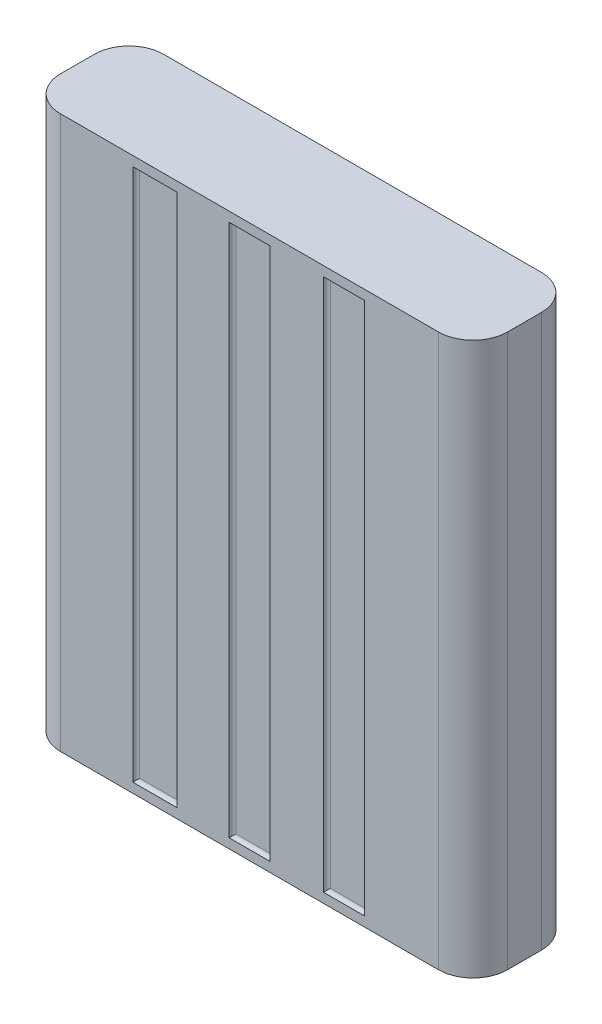
SolidWorks part; units mm, degrees
ref_plane "Front Plane" through (0, 0, 0) normal (0, 0, 1) x (1, 0, 0)
ref_plane "Top Plane" through (0, 0, 0) normal (0, 1, 0) x (1, 0, 0)
ref_plane "Right Plane" through (0, 0, 0) normal (1, 0, 0) x (0, 0, -1)
sketch "Sketch1" plane through (0, 0, 0) normal (0, 1, 0) x (1, 0, 0)
  line L1 (-6.4751, 1.4928) -> (6.4751, 1.4928)
  line L2 (-6.4751, 1.4928) -> (-6.4751, -1.4928)
  line L3 (-6.4751, -1.4928) -> (6.4751, -1.4928)
  line L4 (6.4751, 1.4928) -> (6.4751, -1.4928)
  line L5 (-6.4751, 1.4928) -> (6.4751, -1.4928) construction
  line L6 (-6.4751, -1.4928) -> (6.4751, 1.4928) construction
  point P0 (0, 0)
extrude "Boss-Extrude1" add sketch "Sketch1" along normal blind 16
fillet "Fillet1" radius 1 4 edges at (6.4751, 8, -1.4928) (6.4751, 8, 1.4928) (-6.4751, 8, -1.4928) (-6.4751, 8, 1.4928)
sketch "Sketch2" plane through (0, 0, -1.4928) normal (0, 0, -1) x (-1, 0, 0)
  line L0 (5.4751, 0) -> (5.4751, 16) construction
  line L1 (-5.4751, 10.8394) -> (5.4751, 10.8394)
  line L2 (-5.4751, 10.8394) -> (-5.4751, 10.567)
  line L3 (-5.4751, 10.567) -> (5.4751, 10.567)
  line L4 (5.4751, 10.8394) -> (5.4751, 10.567)
  line L5 (-5.4751, 16) -> (-5.4751, 0) construction
extrude "Boss-Extrude2" add sketch "Sketch2" along normal blind 0.1
fillet "Fillet2" radius 0.1 4 edges at (0, 10.8394, -1.5928) (-5.4751, 10.7032, -1.5928) (0, 10.567, -1.5928) (5.4751, 10.7032, -1.5928)
sketch "Sketch5" plane through (0, 0, -1.5928) normal (0, 0, -1) x (-1, 0, 0)
  line L0 (-5.4751, 10.8394) -> (-5.3751, 10.7394) construction
  line L3 (-5.3751, 10.567) -> (5.4751, 10.567)
  line L4 (5.4751, 10.7394) -> (5.4751, 10.567)
  line L5 (-5.3751, 10.567) -> (-5.4751, 10.567)
  line L7 (-5.3751, 10.8394) -> (-5.4751, 10.8394)
  line L8 (-5.4751, 10.567) -> (-5.4751, 10.8394)
  line L9 (-5.4751, 10.8394) -> (-5.4751, 10.567) construction
  line L11 (-5.3751, 10.8394) -> (5.4751, 10.8394)
  line L14 (5.4751, 10.8394) -> (5.4751, 10.7394)
extrude "Cut-Extrude2" cut sketch "Sketch5" against normal blind 0.1
sketch "Sketch6" plane through (0, 0, -1.4928) normal (0, 0, -1) x (-1, 0, 0)
  line L8 (-3.3309, 15.7209) -> (-2.1442, 15.7209)
  line L9 (-3.3309, 15.7209) -> (-3.3309, 0.2791)
  line L10 (-3.3309, 0.2791) -> (-2.1442, 0.2791)
  line L11 (-2.1442, 15.7209) -> (-2.1442, 0.2791)
  line L14 (-0.5877, 15.7209) -> (0.5877, 15.7209)
  line L15 (-0.5877, 15.7209) -> (-0.5877, 0.2791)
  line L16 (-0.5877, 0.2791) -> (0.5877, 0.2791)
  line L17 (0.5877, 15.7209) -> (0.5877, 0.2791)
  line L20 (2.0968, 15.7209) -> (3.3783, 15.7209)
  line L21 (2.0968, 15.7209) -> (2.0968, 0.2791)
  line L22 (2.0968, 0.2791) -> (3.3783, 0.2791)
  line L23 (3.3783, 15.7209) -> (3.3783, 0.2791)
  point P10 (-2.7375, 8)
  point P22 (2.7375, 8)
extrude "Cut-Extrude3" cut sketch "Sketch6" against normal blind 0.1 contours L23 L22 L21 L20 | L17 L16 L15 L14 | L11 L10 L9 L8
sketch "Sketch10" plane through (0, 0, 1.4928) normal (0, 0, 1) x (1, 0, 0)
  line L1 (3.3309, 15.7209) -> (2.1442, 15.7209)
  line L2 (3.3309, 15.7209) -> (3.3309, 0.2791)
  line L3 (3.3309, 0.2791) -> (2.1442, 0.2791)
  line L4 (2.1442, 15.7209) -> (2.1442, 0.2791)
  line L5 (0.5877, 15.7209) -> (-0.5877, 15.7209)
  line L6 (0.5877, 15.7209) -> (0.5877, 0.2791)
  line L7 (0.5877, 0.2791) -> (-0.5877, 0.2791)
  line L8 (-0.5877, 15.7209) -> (-0.5877, 0.2791)
  line L9 (-2.0968, 15.7209) -> (-3.3783, 15.7209)
  line L10 (-2.0968, 15.7209) -> (-2.0968, 0.2791)
  line L11 (-2.0968, 0.2791) -> (-3.3783, 0.2791)
  line L12 (-3.3783, 15.7209) -> (-3.3783, 0.2791)
extrude "Cut-Extrude4" cut sketch "Sketch10" against normal blind 0.1 contours L6 L5 L8 L7 | L2 L1 L4 L3 | L10 L9 L12 L11
fillet "Fillet6" radius 0.1 12 edges at (2.1442, 8, 1.3928) (2.7375, 15.7209, 1.3928) (3.3309, 8, 1.3928) (2.7375, 0.2791, 1.3928) (-0.5877, 8, 1.3928) (0, 15.7209, 1.3928) (0.5877, 8, 1.3928) (0, 0.2791, 1.3928) (-3.3783, 8, 1.3928) (-2.7375, 15.7209, 1.3928) (-2.0968, 8, 1.3928) (-2.7375, 0.2791, 1.3928)
fillet "Fillet7" radius 0.1 12 edges at (-3.3783, 8, -1.3928) (-2.7375, 0.2791, -1.3928) (-2.0968, 8, -1.3928) (-2.7375, 15.7209, -1.3928) (-0.5877, 8, -1.3928) (0, 0.2791, -1.3928) (0.5877, 8, -1.3928) (0, 15.7209, -1.3928) (2.1442, 8, -1.3928) (2.7375, 0.2791, -1.3928) (3.3309, 8, -1.3928) (2.7375, 15.7209, -1.3928)
scale "Scale1" scale about centroid uniform scaling yes scale factor 3
